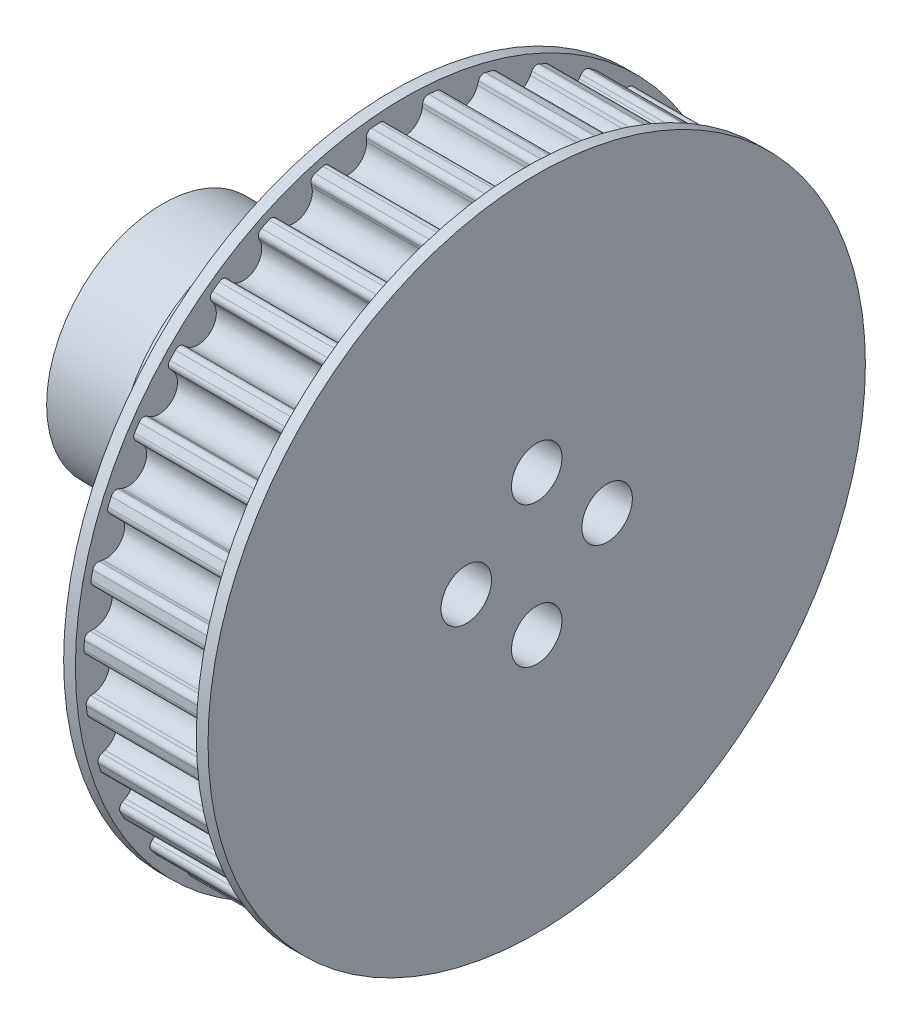
SolidWorks part; units mm, degrees
material "ABS"
ref_plane "前视基准面" through (0, 0, 0) normal (0, 0, 1) x (1, 0, 0)
ref_plane "上视基准面" through (0, 0, 0) normal (0, 1, 0) x (1, 0, 0)
ref_plane "右视基准面" through (0, 0, 0) normal (1, 0, 0) x (0, 0, -1)
sketch "草图1" plane through (0, 0, 0) normal (0, 0, 1) x (1, 0, 0)
  line L0 (0, 0) -> (64.8368, 0) construction
  line L1 (0, 0) -> (0, 27.278)
  line L2 (0, 27.278) -> (10.3, 27.278)
  line L3 (10.3, 27.278) -> (10.3, 0)
  line L6 (10.3, 0) -> (0, 0)
  dimension "B" = 10.3
  dimension "da" = 54.556
revolve "旋转1" add sketch "草图1" angle 360 about L0
ref_axis "基准轴1" through (-1.4, 0, 0) along (1, 0, 0)
sketch "草图6" plane through (0, 0, 0) normal (1, 0, 0) x (0, 0, -1)
  line L0 (0, 0) -> (0, 30.6512) construction
  line L1 (1.5839, 26.7772) -> (1.5484, 26.4879)
  line L2 (2.5954, 27.1543) -> (2.792, 28.7558)
  line L3 (-2.5954, 27.1543) -> (-2.792, 28.7558)
  line L4 (-1.5839, 26.7772) -> (-1.5484, 26.4879)
  circle A0 centre (0, 0) radius 27.278 construction
  circle A1 centre (0, 0) radius 25.118 construction
  arc A2 (-1.5484, 26.4879) -> (1.5484, 26.4879) centre (0, 26.678) ccw
  arc A3 (2.792, 28.7558) -> (-2.792, 28.7558) centre (0, 0) ccw
  arc A4 (1.5839, 26.7772) -> (2.0972, 27.1973) centre (2.0603, 26.7187) cw
  arc A5 (2.0972, 27.1973) -> (2.5954, 27.1543) centre (0, 0) cw
  arc A6 (-2.0972, 27.1973) -> (-2.5954, 27.1543) centre (0, 0) ccw
  arc A7 (-1.5839, 26.7772) -> (-2.0972, 27.1973) centre (-2.0603, 26.7187) ccw
  circle A8 centre (0, 0) radius 27.278 construction
  point P7 (0, 3.25)
  point P8 (0, 28.4912)
  point P15 (1.6393, 27.2287)
  dimension "ra" = 0.48
  dimension "rf" = 1.56
  dimension "hg" = 2.16
  dimension "D3" = 0.5
  dimension "D4" = 1.6136
  dimension "angle" = 14
  dimension "bw" = 3.25
  dimension "D1" = 2.16
extrude "切除-拉伸2" cut sketch "草图6" along normal up to next
pattern_circular "阵列(圆周)3" count 35 over 360 about axis through (-1.4, 0, 0) along (1, 0, 0) of "切除-拉伸2"
sketch "草图7" plane through (10.3, 0, 0) normal (1, 0, 0) x (0, 0, -1)
  circle A0 centre (0, 0) radius 28
  dimension "D1" = 56
extrude "凸台-拉伸1" add sketch "草图7" along normal blind 1
sketch "草图8" plane through (0, 0, 0) normal (-1, 0, 0) x (0, 0, 1)
  circle A0 centre (0, 0) radius 28
  circle A1 centre (0, 0) radius 28 construction
extrude "凸台-拉伸2" add sketch "草图8" along normal blind 1
sketch "草图9" plane through (-1, 0, 0) normal (-1, 0, 0) x (0, 0, 1)
  circle A0 centre (0, 0) radius 12
  dimension "D1" = 24
extrude "凸台-拉伸3" add sketch "草图9" along normal blind 11.55
sketch "草图10" plane through (-12.55, 0, 0) normal (-1, 0, 0) x (0, 0, 1)
  circle A0 centre (0, 0) radius 9.9
  dimension "D1" = 19.8
extrude "凸台-拉伸4" add sketch "草图10" along normal blind 8
sketch "草图11" plane through (-20.55, 0, 0) normal (-1, 0, 0) x (0, 0, 1)
  circle A0 centre (0, 0) radius 6 construction
  circle A1 centre (0, 6) radius 2.15
  circle A2 centre (6, 0) radius 2.15
  circle A3 centre (0, -6) radius 2.15
  circle A4 centre (-6, 0) radius 2.15
  dimension "D1" = 12
  dimension "D3" = 4.3
  dimension "D2" = 4
extrude "切除-拉伸3" cut sketch "草图11" against normal through all
equation "\"D3@草图6\" = \"ra@草图6\""
